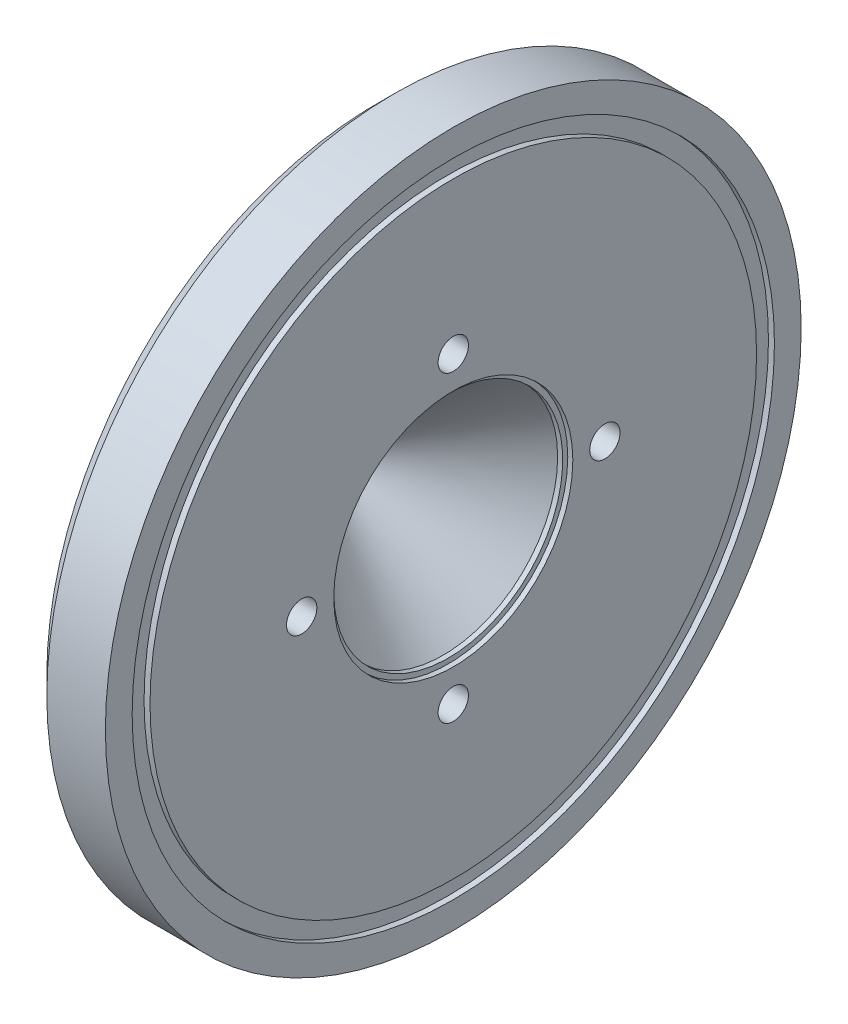
SolidWorks part; units mm, degrees
ref_plane "Front Plane" through (0, 0, 0) normal (0, 0, 1) x (1, 0, 0)
ref_plane "Top Plane" through (0, 0, 0) normal (0, 1, 0) x (1, 0, 0)
ref_plane "Right Plane" through (0, 0, 0) normal (1, 0, 0) x (0, 0, -1)
sketch "Sketch1" plane through (0, 0, 0) normal (0, 0, 1) x (1, 0, 0)
  line L0 (-801.9206, 0) -> (36107.5283, 0) construction
  line L3 (-14.1752, 3.65) -> (-14.1752, 3.15)
  line L8 (-18.5085, 1.9) -> (0, 1.9)
  line L9 (-18.5085, 1.9) -> (-18.5085, 3.15)
  line L10 (13.1623, 13.4) -> (13.1623, 39)
  line L12 (13.1623, 39) -> (4.5963, 39)
  line L16 (13.1623, 13.4) -> (12.5963, 13.4)
  line L17 (12.5963, 13.4) -> (12.5963, 12.834)
  line L18 (4.5963, 39) -> (4.5963, 12.834)
  line L20 (0, 1.9) -> (12.0303, 12.834)
  line L21 (-18.5085, 3.15) -> (-14.1752, 3.65)
  line L22 (12.0303, 12.834) -> (12.5963, 12.834)
  line L23 (-14.1752, 3.15) -> (-9.8419, 3.65)
  line L25 (-9.8419, 3.15) -> (-5.5085, 3.65)
  line L26 (-9.8419, 3.65) -> (-9.8419, 3.15)
  line L27 (-5.5085, 3.65) -> (4.5963, 12.834)
  line L29 (12.4953, 36) -> (12.4953, 34)
  line L30 (12.4953, 34) -> (13.1623, 34)
  line L32 (12.4953, 36) -> (13.1623, 36)
  dimension "D3" = 0.566
  dimension "D2" = 7.3
  dimension "D6" = 3.8
  dimension "D7" = 6.3
  dimension "D5" = 39
  dimension "D8" = 13.4
  dimension "D10" = 0.566
  dimension "D4" = 5
  dimension "D9" = 0.566
  dimension "D11" = 13
  dimension "D12" = 8.566
  dimension "D14" = 2
  dimension "D13" = 36
  dimension "D15" = 0.667
revolve "Revolve17" add sketch "Sketch1" angle 360 about L0 region at (6.0149, 19.9157, 0)
sketch "Sketch4" plane through (4.5963, 0, 0) normal (-1, 0, 0) x (0, 0, 1)
  circle A0 centre (0, 0) radius 16.9947 construction
  point P3 (0, 16.9947)
  point P7 (16.9947, 0)
  point P12 (-16.9947, 0)
  point P13 (0, -16.9947)
hole_wizard "CBORE for M3 Hex Socket Head Cap Screw2" positions "Sketch4" profile "Sketch5" counterbore size "M3" standard "ISO"
sketch "Sketch5" plane through (4.5963, -16.9947, 0) normal (0, 1, 0) x (0, 0, 1)
  line L0 (0, 0) -> (0, 9.5875)
  line L1 (0, 9.5875) -> (1.7, 8.566)
  line L2 (1.7, 8.566) -> (1.7, 3.4)
  line L3 (1.7, 3.4) -> (3.25, 3.4)
  line L4 (3.25, 3.4) -> (3.25, 0)
  line L5 (3.25, 0) -> (0, 0)
  line L10 (0, 9.5875) -> (-1.7, 8.566) construction
  line L11 (0, -6.35) -> (0, 107.95) construction
  dimension "Hole Dia." = 3.4
  dimension "Hole Depth" = 8.566
  dimension "C'Bore Dia." = 6.5
  dimension "C'Bore Depth" = 3.4
  dimension "Drill Angle" = 118
chamfer "Chamfer1" distance 2 angle 45 1 edges at (4.5963, 0, 39)
equation "\"D10@Sketch1\"=\"D3@Sketch1\""
equation "\"D9@Sketch1\"=\"D3@Sketch1\""
